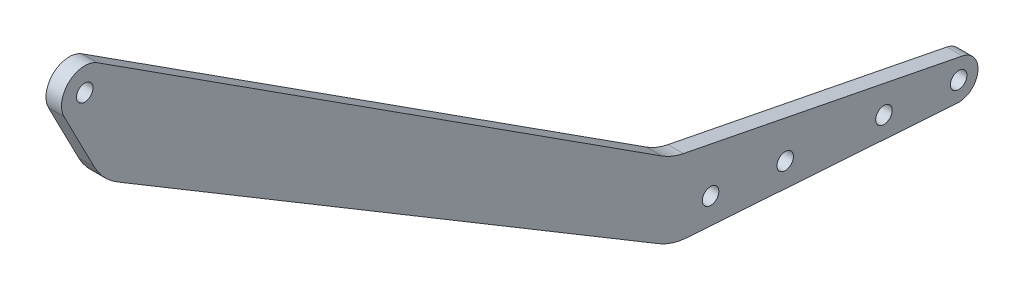
SolidWorks part; units mm, degrees
ref_plane "Front Plane" through (0, 0, 0) normal (0, 0, 1) x (1, 0, 0)
ref_plane "Top Plane" through (0, 0, 0) normal (0, 1, 0) x (1, 0, 0)
ref_plane "Right Plane" through (0, 0, 0) normal (1, 0, 0) x (0, 0, -1)
ref_plane "Plane1" through (-76.9133, 0, 0) normal (1, 0, 0) x (0, 0, -1)
sketch "Sketch1" plane through (-76.9133, 0, 0) normal (1, 0, 0) x (0, 0, -1)
  line L0 (535.7661, 896.8306) -> (535.7661, 915.8806) construction
  line L1 (434.1661, 906.5188) -> (434.1661, 925.5688) construction
  line L2 (177.8, 1090.4307) -> (434.1661, 925.5688) construction
  line L3 (139.7, 1090.4307) -> (177.8, 1090.4307) construction
  line L4 (535.7661, 896.8306) -> (535.7661, 915.8806) construction
  line L5 (434.1661, 906.5188) -> (434.1661, 925.5688) construction
  line L6 (177.8, 1090.4307) -> (434.1661, 925.5688) construction
  line L7 (139.7, 1090.4307) -> (177.8, 1090.4307) construction
  line L8 (535.2188, 907.962) -> (418.2911, 916.0438)
  line L9 (537.2996, 923.6685) -> (418.2911, 947.1021)
  line L10 (169.3326, 1086.0686) -> (184.9514, 1055.7506)
  line L11 (184.9514, 1055.7506) -> (418.2911, 916.0438)
  line L12 (418.2911, 947.1021) -> (182.9519, 1098.4422)
  line L13 (434.1661, 925.5688) -> (535.7661, 915.8806) construction
  circle A0 centre (177.8, 1090.4307) radius 3.3782
  circle A1 centre (434.1661, 925.5688) radius 3.3782
  circle A2 centre (535.7661, 915.8806) radius 3.3782
  arc A3 (535.2188, 907.962) -> (537.2996, 923.6685) centre (535.7661, 915.8806) ccw
  arc A5 (182.9519, 1098.4422) -> (169.3326, 1086.0686) centre (177.8, 1090.4307) ccw
  arc A6 (537.2996, 923.6685) -> (535.2188, 907.962) centre (535.7661, 915.8806) ccw construction
  arc A7 (169.3326, 1086.0686) -> (185.8114, 1085.2788) centre (177.8, 1090.4307) ccw construction
  arc A8 (185.8114, 1085.2788) -> (182.9519, 1098.4422) centre (177.8, 1090.4307) ccw construction
  circle A9 centre (464.7144, 922.6558) radius 3.3782
  circle A10 centre (505.1709, 918.798) radius 3.3782
  spline S0 degree 3 poles (935.6767, 939.7163) (940.3147, 942.1548) (935.2529, 940.0507) (930.9716, 938.764) (920.6916, 935.461) (907.9553, 931.9087) (891.2949, 927.4743) (871.5218, 922.6042) (848.5739, 917.4165) (822.7695, 912.1503) (794.3904, 907.0475) (763.8436, 902.4482) (731.6326, 898.5836) (698.2942, 895.5048) (664.3294, 893.3038) (630.2914, 892.1587) (596.9177, 892.4579) (565.0805, 894.155) (535.5455, 896.7257) (508.8897, 899.7641) (485.4664, 902.8148) (465.3261, 905.1664) (448.3721, 906.4646) (434.4368, 906.7165) (423.4463, 905.9074) (416.5733, 904.5379) (412.9407, 903.1204) (411.5732, 902.4729) (410.4746, 901.8174) (409.7947, 901.3358) (409.3397, 900.9203) (409.0422, 900.6195) (408.7846, 900.3039) (408.5873, 899.9553) (408.4178, 899.5844) (408.2374, 899.0451) (408.051, 898.3239) (407.9116, 897.2265) (407.8599, 894.9991) (408.6865, 890.8402) (411.376, 884.946) (416.2539, 878.2548) (423.1327, 871.4111) (431.9816, 864.5947) (442.7539, 857.9825) (455.382, 851.7275) (469.765, 845.9615) (485.7865, 840.8065) (503.3041, 836.37) (522.1586, 832.7575) (542.1676, 830.0521) (563.1459, 828.3505) (584.9266, 827.7965) (607.3492, 828.4639) (630.2782, 830.4035) (653.5854, 833.657) (677.1845, 838.2437) (700.9897, 844.1113) (724.9284, 850.9153) (748.8232, 858.3979) (772.4019, 866.3681) (795.3921, 874.6046) (817.5075, 882.9123) (838.4515, 891.1278) (857.9391, 899.0809) (875.6775, 906.6433) (891.4161, 913.7156) (904.9213, 920.2497) (916.21, 926.5709) (924.8872, 932.3286) (932.3848, 937.3638) (935.6767, 939.7163) (940.3147, 942.1548) (935.2529, 940.0507) knots -0.014576 -0.006911 -0.001813 0 0.001841 0.007308 0.016237 0.028456 0.043801 0.062126 0.08324 0.106896 0.132817 0.160613 0.189791 0.219873 0.250457 0.281127 0.311257 0.339999 0.366671 0.390812 0.411995 0.430069 0.445224 0.457619 0.467425 0.474786 0.47628 0.477884 0.47884 0.479711 0.480113 0.480492 0.480846 0.481203 0.481564 0.48194 0.482727 0.483559 0.484903 0.488692 0.494806 0.502149 0.510796 0.520764 0.532062 0.544666 0.558541 0.573612 0.589803 0.60701 0.625107 0.643967 0.663469 0.683551 0.704142 0.725196 0.74668 0.768633 0.790977 0.813463 0.835827 0.857772 0.879003 0.899228 0.918151 0.935487 0.950987 0.964428 0.975828 0.985424 0.993089 0.998187 1 1.001841 1.007308 1.016237 only from (939.324, 941.6889) to (939.324, 941.6889) construction
  spline S1 degree 3 poles (935.6767, 939.7163) (940.3147, 942.1548) (935.2529, 940.0507) (930.9716, 938.764) (920.6916, 935.461) (907.9553, 931.9087) (891.2949, 927.4743) (871.5218, 922.6042) (848.5739, 917.4165) (822.7695, 912.1503) (794.3904, 907.0475) (763.8436, 902.4482) (731.6326, 898.5836) (698.2942, 895.5048) (664.3294, 893.3038) (630.2914, 892.1587) (596.9177, 892.4579) (565.0805, 894.155) (535.5455, 896.7257) (508.8897, 899.7641) (485.4664, 902.8148) (465.3261, 905.1664) (448.3721, 906.4646) (434.4368, 906.7165) (423.4463, 905.9074) (416.5733, 904.5379) (412.9407, 903.1204) (411.5732, 902.4729) (410.4746, 901.8174) (409.7947, 901.3358) (409.3397, 900.9203) (409.0422, 900.6195) (408.7846, 900.3039) (408.5873, 899.9553) (408.4178, 899.5844) (408.2374, 899.0451) (408.051, 898.3239) (407.9116, 897.2265) (407.8599, 894.9991) (408.6865, 890.8402) (411.376, 884.946) (416.2539, 878.2548) (423.1327, 871.4111) (431.9816, 864.5947) (442.7539, 857.9825) (455.382, 851.7275) (469.765, 845.9615) (485.7865, 840.8065) (503.3041, 836.37) (522.1586, 832.7575) (542.1676, 830.0521) (563.1459, 828.3505) (584.9266, 827.7965) (607.3492, 828.4639) (630.2782, 830.4035) (653.5854, 833.657) (677.1845, 838.2437) (700.9897, 844.1113) (724.9284, 850.9153) (748.8232, 858.3979) (772.4019, 866.3681) (795.3921, 874.6046) (817.5075, 882.9123) (838.4515, 891.1278) (857.9391, 899.0809) (875.6775, 906.6433) (891.4161, 913.7156) (904.9213, 920.2497) (916.21, 926.5709) (924.8872, 932.3286) (932.3848, 937.3638) (935.6767, 939.7163) (940.3147, 942.1548) (935.2529, 940.0507) knots -0.014576 -0.006911 -0.001813 0 0.001841 0.007308 0.016237 0.028456 0.043801 0.062126 0.08324 0.106896 0.132817 0.160613 0.189791 0.219873 0.250457 0.281127 0.311257 0.339999 0.366671 0.390812 0.411995 0.430069 0.445224 0.457619 0.467425 0.474786 0.47628 0.477884 0.47884 0.479711 0.480113 0.480492 0.480846 0.481203 0.481564 0.48194 0.482727 0.483559 0.484903 0.488692 0.494806 0.502149 0.510796 0.520764 0.532062 0.544666 0.558541 0.573612 0.589803 0.60701 0.625107 0.643967 0.663469 0.683551 0.704142 0.725196 0.74668 0.768633 0.790977 0.813463 0.835827 0.857772 0.879003 0.899228 0.918151 0.935487 0.950987 0.964428 0.975828 0.985424 0.993089 0.998187 1 1.001841 1.007308 1.016237 only from (939.324, 941.6889) to (939.324, 941.6889) construction
  dimension "D1" = 6.7564
  dimension "D2" = 6.7564
  dimension "D3" = 6.7564
  dimension "D4" = 15.875
  dimension "D5" = 30
  dimension "D6" = 19.05
  dimension "D10" = 6.7564
  dimension "D11" = 6.7564
  dimension "D7" = 148.166
  dimension "D8" = 15.875
  dimension "D9" = 9.525
  dimension "D12" = 40.64
  dimension "D13" = 30.734
extrude "Boss-Extrude1" add sketch "Sketch1" along normal mid plane 6.35
fillet "Fillet1" radius 25.4 3 edges at (-76.9133, 1055.7506, -184.9514) (-76.9133, 947.1021, -418.2911) (-76.9133, 916.0438, -418.2911)
